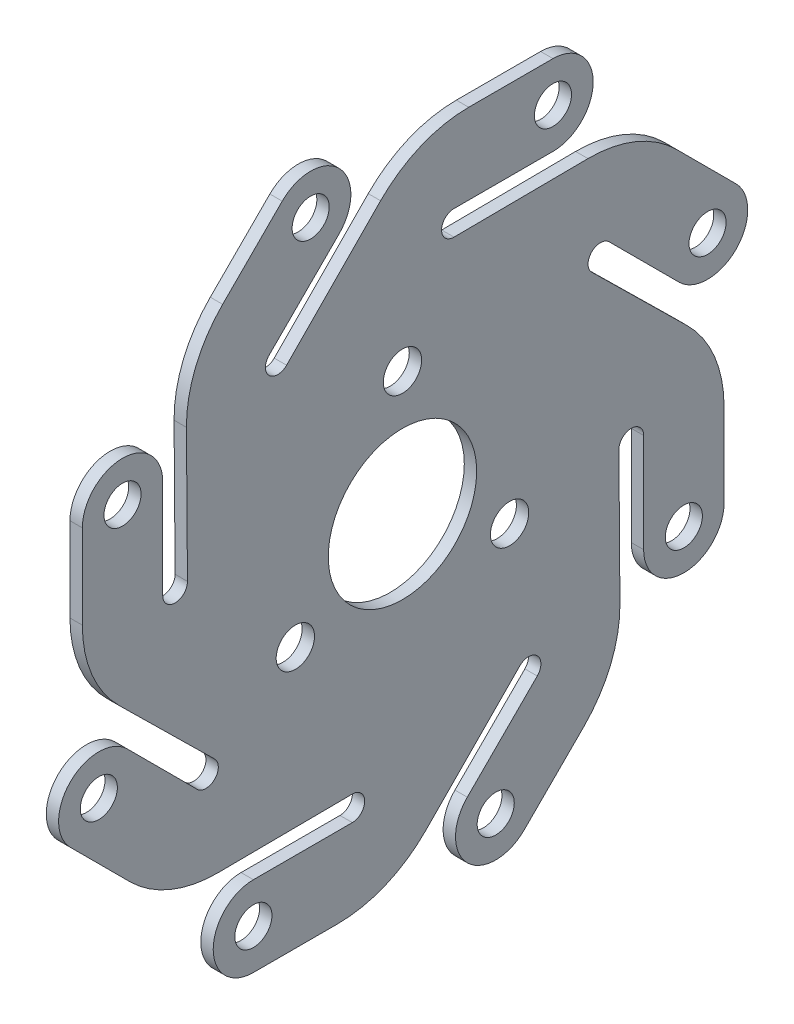
SolidWorks part; units mm, degrees
ref_plane "Front Plane" through (0, 0, 0) normal (0, 0, 1) x (1, 0, 0)
ref_plane "Top Plane" through (0, 0, 0) normal (0, 1, 0) x (1, 0, 0)
ref_plane "Right Plane" through (0, 0, 0) normal (1, 0, 0) x (0, 0, -1)
sketch "Sketch1" plane through (0, 0, 0) normal (1, 0, 0) x (0, 0, -1)
  line L0 (-30.1425, 0) -> (30.1425, 0) construction
  line L1 (26.0002, 0) -> (26.0002, -15.25) construction
  line L2 (19.5, -12.25) -> (19.5, -4.25) construction
  line L3 (15.2984, 9.2874) -> (26.0002, -1.25) construction
  line L4 (15.2984, 9.2874) -> (23.0163, 1.688)
  line L5 (26.0002, -5.4375) -> (26.0002, -12.25)
  line L6 (19.5, -12.25) -> (19.5, -4.25)
  line L7 (17.5, -4.25) -> (17.5838, -15.081)
  line L8 (14.6552, -22.2294) -> (9.838, -27.0466)
  line L9 (5.2417, -22.4503) -> (10.8986, -16.7934)
  line L10 (9.4844, -15.3792) -> (1.8849, -23.0971)
  line L11 (-5.2406, -26.081) -> (-12.0531, -26.081)
  line L12 (-12.0531, -19.5808) -> (-4.0531, -19.5808)
  line L13 (-4.0531, -17.5808) -> (-14.8841, -17.6646)
  line L14 (-22.0325, -14.736) -> (-26.8496, -9.9188)
  line L15 (-22.2533, -5.3225) -> (-16.5965, -10.9794)
  line L16 (-15.1823, -9.5652) -> (-22.9002, -1.9658)
  line L17 (-25.884, 5.1598) -> (-25.884, 11.9723)
  line L18 (-19.3839, 11.9723) -> (-19.3839, 3.9723)
  line L19 (-17.3839, 3.9723) -> (-17.4677, 14.8033)
  line L20 (-14.5391, 21.9517) -> (-9.7219, 26.7688)
  line L21 (-5.1256, 22.1725) -> (-10.7825, 16.5157)
  line L22 (-9.3683, 15.1015) -> (-1.7688, 22.8194)
  line L23 (5.3567, 25.8032) -> (12.1692, 25.8032)
  line L24 (12.1692, 19.3031) -> (4.1692, 19.3031)
  line L25 (4.1692, 17.3031) -> (15.0002, 17.3869)
  line L26 (22.1486, 14.4582) -> (26.9658, 9.6411)
  line L27 (22.3695, 5.0448) -> (16.7126, 10.7017)
  circle A0 centre (0, 0) radius 30.1425 construction
  circle A1 centre (16, 10) radius 1 construction
  circle A2 centre (18.5, -4.25) radius 1 construction
  circle A3 centre (22.7501, -12.25) radius 1.5
  arc A4 (26.0002, -12.25) -> (19.5, -12.25) centre (22.7501, -12.25) cw
  arc A5 (26.0002, -5.4375) -> (23.0163, 1.688) centre (16.0002, -5.4375) ccw
  arc A6 (14.6552, -22.2294) -> (17.5838, -15.081) centre (7.5841, -15.1584) ccw
  arc A7 (9.838, -27.0466) -> (5.2417, -22.4503) centre (7.5399, -24.7484) cw
  circle A8 centre (7.5399, -24.7484) radius 1.5
  arc A9 (-5.2406, -26.081) -> (1.8849, -23.0971) centre (-5.2406, -16.081) ccw
  arc A10 (-12.0531, -26.081) -> (-12.0531, -19.5808) centre (-12.0531, -22.8309) cw
  circle A11 centre (-12.0531, -22.8309) radius 1.5
  arc A12 (-22.0325, -14.736) -> (-14.8841, -17.6646) centre (-14.9614, -7.6649) ccw
  arc A13 (-26.8496, -9.9188) -> (-22.2533, -5.3225) centre (-24.5515, -7.6207) cw
  circle A14 centre (-24.5515, -7.6207) radius 1.5
  arc A15 (-25.884, 5.1598) -> (-22.9002, -1.9658) centre (-15.884, 5.1598) ccw
  arc A16 (-25.884, 11.9723) -> (-19.3839, 11.9723) centre (-22.634, 11.9723) cw
  circle A17 centre (-22.634, 11.9723) radius 1.5
  arc A18 (-14.5391, 21.9517) -> (-17.4677, 14.8033) centre (-7.468, 14.8806) ccw
  arc A19 (-9.7219, 26.7688) -> (-5.1256, 22.1725) centre (-7.4238, 24.4707) cw
  circle A20 centre (-7.4238, 24.4707) radius 1.5
  arc A21 (5.3567, 25.8032) -> (-1.7688, 22.8194) centre (5.3567, 15.8032) ccw
  arc A22 (12.1692, 25.8032) -> (12.1692, 19.3031) centre (12.1692, 22.5532) cw
  circle A23 centre (12.1692, 22.5532) radius 1.5
  arc A24 (22.1486, 14.4582) -> (15.0002, 17.3869) centre (15.0775, 7.3872) ccw
  arc A25 (26.9658, 9.6411) -> (22.3695, 5.0448) centre (24.6676, 7.343) cw
  circle A26 centre (24.6676, 7.343) radius 1.5
  arc A27 (19.5, -4.25) -> (17.5, -4.25) centre (18.5, -4.25) ccw
  arc A28 (15.2984, 9.2874) -> (16.7126, 10.7017) centre (16.0055, 9.9946) cw
  circle A29 centre (0, 0) radius 6
  arc A30 (9.4844, -15.3792) -> (10.8986, -16.7934) centre (10.1915, -16.0863) cw
  arc A31 (-4.0531, -17.5808) -> (-4.0531, -19.5808) centre (-4.0531, -18.5808) cw
  arc A32 (-15.1823, -9.5652) -> (-16.5965, -10.9794) centre (-15.8894, -10.2723) cw
  arc A33 (-19.3839, 3.9723) -> (-17.3839, 3.9723) centre (-18.3839, 3.9645) ccw
  arc A34 (-10.7825, 16.5157) -> (-9.3683, 15.1015) centre (-10.0808, 15.8031) ccw
  arc A35 (4.1692, 19.3031) -> (4.1692, 17.3031) centre (4.1615, 18.3031) ccw
  circle A36 centre (0, 10) radius 1.55
  circle A37 centre (8.6603, -5) radius 1.55
  circle A38 centre (-8.6603, -5) radius 1.55
  point P95 (0.0581, -0.1389)
  point P105 (0.0581, -0.1389)
  point P106 (0, 0)
  point P110 (0, 0)
  point P111 (0, 0)
  point P112 (0.0581, -0.1389)
  point P113 (0, 0)
  point P114 (0, 0)
  point P115 (0, 0)
  point P116 (0.0581, -0.1389)
  dimension "D1" = 60.285
  dimension "D4" = 2
  dimension "D7" = 2
  dimension "D9" = 3
  dimension "D12" = 10
  dimension "D14" = 12
  dimension "D15" = 3.1
  dimension "D2" = 10
  dimension "D3" = 16
  dimension "D5" = 4.25
  dimension "D6" = 18.5
  dimension "D8" = 15.25
  dimension "D10" = 8
  dimension "D11" = 1.25
  dimension "D16" = 10
  dimension "D13" = 8
  dimension "D17" = 3
base flange "Base-Flange1" sketch "Sketch1" thickness 1 reverse thickness direction no parameters "D1"=0.7366
sketch "Sketch6" plane through (0, 0, 0) normal (1, 0, 0) x (0, 0, -1)
  line L0 (19.5, -7.1368) -> (26.0002, -7.1368)
  line L1 (19.5, -12.25) -> (19.5, -4.25) construction
  line L2 (26.0002, -5.4375) -> (26.0002, -12.25) construction
  line L3 (8.7421, -18.8351) -> (13.3384, -23.4314)
  line L4 (-7.1368, -19.5) -> (-7.1368, -26.0002)
  line L5 (-18.8351, -8.7421) -> (-23.4314, -13.3384)
  line L6 (-19.5, 7.1368) -> (-26.0002, 7.1368)
  line L7 (-8.7421, 18.8351) -> (-13.3384, 23.4314)
  line L8 (7.1368, 19.5) -> (7.1368, 26.0002)
  line L9 (18.8351, 8.7421) -> (23.4314, 13.3384)
  circle A0 centre (0, 0) radius 6 construction
  point P6 (0, 0)
  point P24 (0, 0)
  point P27 (0, 0)
  point P28 (0, 0)
  point P29 (0, 0)
  point P30 (19.5, -7.1368)
  dimension "D1" = 5.1132
  dimension "D2" = 8
sketch "Bend-Lines1" [suppressed] plane through (0, 0, 0) normal (0, 1, 0) x (1, 0, 0)
sketch "Bounding-Box1" [suppressed] plane through (0, 0, 0) normal (0, 1, 0) x (1, 0, 0)
sheet metal parameters "Sheet-Metal1" thickness 1 parameters "D1"=0.7366
flat pattern "Flat-Pattern1" [suppressed]
sketch "Bend-Lines2" plane through (0, 0, 0) normal (0, 1, 0) x (1, 0, 0)
sketch3d "Bounding-Box2" [suppressed]
  line L0 (1.5624, -17.4051, 0) -> (-52.2082, -12.1433, 0) construction
  line L1 (6.8242, 36.3656, 0) -> (-46.9465, 41.6273, 0) construction
  line L2 (1.5624, -17.4051, 0) -> (6.8242, 36.3656, 0) construction
  line L3 (-52.2082, -12.1433, 0) -> (-46.9465, 41.6273, 0) construction
